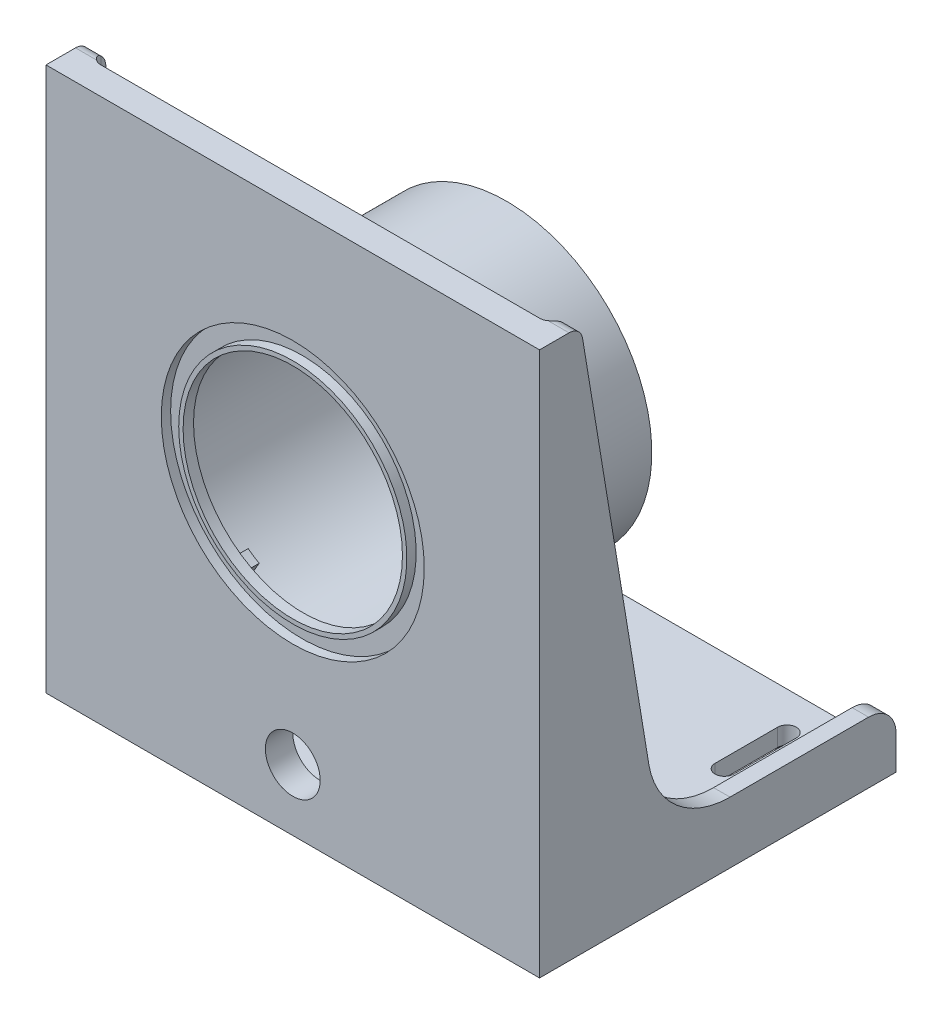
SolidWorks part; units mm, degrees
ref_plane "Front Plane" through (0, 0, 0) normal (0, 0, 1) x (1, 0, 0)
ref_plane "Top Plane" through (0, 0, 0) normal (0, 1, 0) x (1, 0, 0)
ref_plane "Right Plane" through (0, 0, 0) normal (1, 0, 0) x (0, 0, -1)
sketch "Sketch1" plane through (0, 0, 0) normal (0, 0, 1) x (1, 0, 0)
  line L0 (-45, -45) -> (-45, -55)
  line L1 (-45, 45) -> (45, 45)
  line L2 (-45, 45) -> (-45, -45)
  line L3 (-45, -45) -> (45, -45) construction
  line L4 (45, 45) -> (45, -45)
  line L5 (-45, 45) -> (45, -45) construction
  line L6 (-45, -45) -> (45, 45) construction
  line L7 (-45, -55) -> (45, -55)
  line L8 (45, -55) -> (45, -45)
  circle A0 centre (0, 0) radius 23.975
  point P0 (0, 0)
  dimension "D3" = 47.95
  dimension "D1" = 55
  dimension "D2" = 90
extrude "Boss-Extrude1" add sketch "Sketch1" along normal blind 5
sketch "Sketch9" plane through (0, 0, 0) normal (1, 0, 0) x (0, 0, -1)
  line L0 (0, 45) -> (0, -55)
  line L1 (0, -55) -> (60, -55)
  line L2 (60, -55) -> (60, -48)
  line L3 (55, -43) -> (29.7307, -43)
  line L4 (14.9302, -30.4387) -> (2.845, 42.9065)
  line L5 (0.3782, 45) -> (0, 45)
  line L6 (0, -55) -> (0, 45) construction
  line L7 (-5, 45) -> (0, 45) construction
  line L8 (-5, -55) -> (0, -55) construction
  line L9 (17, -43) -> (0, -43) construction
  arc A0 (2.845, 42.9065) -> (0.3782, 45) centre (0.3782, 42.5) ccw
  arc A1 (14.9302, -30.4387) -> (29.7307, -43) centre (29.7307, -28) ccw
  arc A2 (60, -48) -> (55, -43) centre (55, -48) ccw
  point P17 (2.5, 45)
  point P23 (60, -43)
  dimension "D5" = 2.5
  dimension "D6" = 15
  dimension "D7" = 5
  dimension "D1" = 12
  dimension "D2" = 2.5
  dimension "D3" = 60
  dimension "D4" = 43
extrude "Boss-Extrude6" add sketch "Sketch9" along normal mid plane 90
sketch "Sketch10" plane through (0, 0, 0) normal (1, 0, 0) x (0, 0, -1)
  line L0 (0, 45) -> (0, -51)
  line L1 (0, -51) -> (62.7882, -51)
  line L2 (62.7882, -51) -> (2.5, 45)
  line L3 (2.5, 45) -> (0, 45)
  line L4 (-5, -55) -> (60, -55) construction
  line L5 (-5, -55) -> (-5, 45) construction
  line L6 (-5, 45) -> (0.3782, 45) construction
  arc A0 (60, -48) -> (55, -43) centre (55, -48) ccw construction
  dimension "D1" = 4
  dimension "D2" = 5
extrude "Cut-Extrude3" cut sketch "Sketch10" against normal mid plane 84
ref_plane "Plane1" through (23.975, 0, 0) normal (-1, 0, 0) x (0, 0, 1)
sketch "Sketch2" plane through (23.975, 0, 0) normal (-1, 0, 0) x (0, 0, 1)
  line L2 (0, -2.4) -> (3.3, -2.4)
  line L3 (3.3, -2.4) -> (3.3, 14.5)
  line L4 (3.3, 14.5) -> (2.5, 14.5)
  line L5 (2.5, 14.5) -> (1.8, 0)
  line L6 (1.8, 0) -> (0, 0)
  line L7 (0, 0) -> (0, -2.4)
  line L8 (5, 45) -> (5, -55) construction
  dimension "D1" = 1.7
  dimension "D2" = 2.4
  dimension "D3" = 16.9
  dimension "D4" = 3.2
  dimension "D5" = 2.5
extrude "Boss-Extrude3" add sketch "Sketch2" along normal blind 10
sketch "Sketch4" plane through (0, 0, 0) normal (0, 0, 1) x (1, 0, 0)
  line L0 (16.6375, 17.2625) -> (0, 0)
  line L1 (0, 0) -> (19.3599, 14.142)
  arc A0 (19.3599, 14.142) -> (16.6375, 17.2625) centre (0, 0) ccw
  circle A1 centre (0, 0) radius 23.975 construction
extrude "Cut-Extrude2" cut sketch "Sketch4" along normal through all
ref_axis "Axis1" through (0, 0, 0) along (0, 0, 1)
pattern_circular "CirPattern1" count 3 over 360 about axis through (0, 0, 0) along (0, 0, 1) of "Boss-Extrude3", "Cut-Extrude2"
sketch "Sketch3" plane through (0, 0, 0) normal (0, 0, 1) x (1, 0, 0)
  circle A0 centre (0, 0) radius 22.25
  dimension "D1" = 44.5
extrude "Cut-Extrude1" cut sketch "Sketch3" along normal through all
sketch "Sketch5" plane through (0, 0, 3.3) normal (0, 0, 1) x (1, 0, 0)
  circle A0 centre (0, 0) radius 23.975
  circle A1 centre (0, 0) radius 23.975 construction
  circle A2 centre (0, 0) radius 20
  dimension "D1" = 40
extrude "Boss-Extrude4" add sketch "Sketch5" against normal blind 0.2
sketch "Sketch6" plane through (0, 0, 3.3) normal (0, 0, 1) x (1, 0, 0)
  circle A0 centre (0, 0) radius 20
  circle A1 centre (0, 0) radius 20.8
  dimension "D1" = 0.8
extrude "Boss-Extrude5" add sketch "Sketch6" along normal up to surface (1.7 mm away) up to face at (0, -5, 5)
sketch "Sketch8" plane through (0, 0, 0) normal (1, 0, 0) x (0, 0, -1)
  line L0 (0, 23.975) -> (0, 26.475)
  line L2 (0, 26.475) -> (34, 26.475)
  line L10 (0, 23.975) -> (34, 23.975)
  line L12 (34, 23.975) -> (34, 26.475)
  line L13 (0, -19.2691) -> (0, -17.9566) construction
  dimension "D1" = 34
  dimension "D2" = 2.5
revolve "Revolve1" add sketch "Sketch8" angle 360 about axis through (0, 0, 0) along (0, 0, 1)
hole_wizard "M3 Clearance Slot3" positions "Sketch11" profile "Sketch13" size "M3" standard "ISO" slot yes end condition through all
sketch "Sketch11" plane through (0, -43, 0) normal (0, 1, 0) x (1, 0, 0)
  line L0 (-32, 54.8228) -> (-32, 40) construction
  line L1 (45, 60) -> (-45, 60) construction
  line L2 (0, -35.75) -> (0, 35.75) construction
  line L3 (32, 54.8228) -> (32, 40) construction
  line L5 (-42, 0) -> (-42, 60) construction
  point P0 (-32, 47.4114)
  point P14 (32, 47.4114)
  dimension "D1" = 20
  dimension "D2" = 10
sketch "Sketch13" plane through (-32, -43, -47.4114) normal (1, 0, 0) x (0, 0, 1)
  line L0 (0, 0) -> (0, 12)
  line L1 (0, 12) -> (1.7, 12)
  line L2 (1.7, 12) -> (1.7, 0)
  line L5 (1.7, 0) -> (0, 0)
  line L11 (0, -6.35) -> (0, 107.95) construction
  dimension "Thru Hole Dia." = 3.4
  dimension "Thru Hole Depth" = 12
sketch "Sketch14" plane through (0, 0, 5) normal (0, 0, 1) x (1, 0, 0)
  line L0 (-45, -38) -> (45, -38) construction
  line L1 (-45, 45) -> (-45, -55) construction
  line L2 (45, -55) -> (45, 45) construction
  line L3 (-45, -55) -> (45, -55) construction
  line L4 (0, -30.4387) -> (0, 42.9065) construction
  circle A0 centre (0, -43) radius 5
  circle A1 centre (0, 0) radius 33 construction
  dimension "D2" = 10
  dimension "D3" = 66
  dimension "D1" = 17
extrude "Cut-Extrude4" cut sketch "Sketch14" against normal through all
ref_axis "Axis2" through (0, -43, 0) along (0, 0, 1)
fillet "Fillet3" radius 2 5 edges at (42, -3, 0) (0, -51, 0) (-42, -3, 0) (42, -51, -30) (-42, -51, -30)
chamfer "Chamfer1" distance 0.8 angle 45 12 edges at (0, -55, 5) (0, -55, -60) (32, -55, -54.8228) (33.7, -55, -47.4114) (32, -55, -40) (30.3, -55, -47.4114) (-32, -55, -54.8228) (-30.3, -55, -47.4114) (-32, -55, -40) (-33.7, -55, -47.4114) (45, -55, -27.5) (-45, -55, -27.5)
